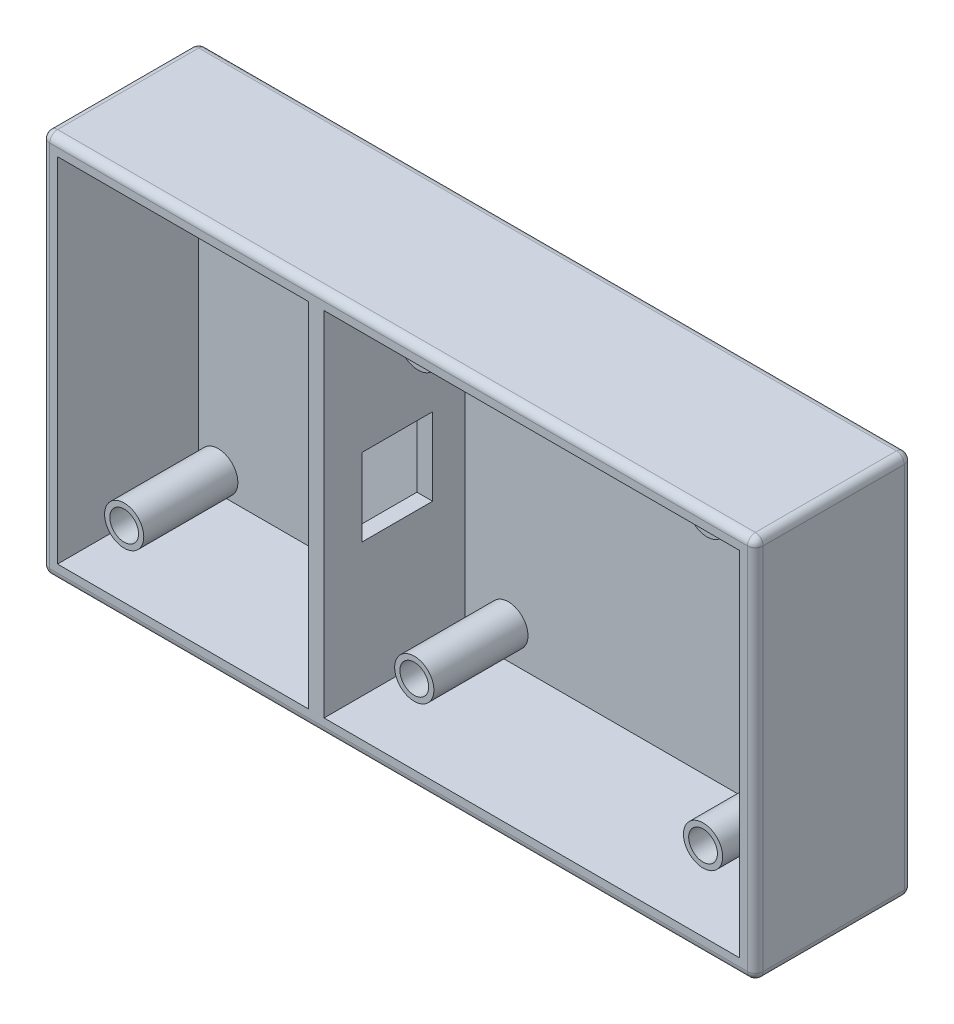
SolidWorks part; units mm, degrees
ref_plane "Front Plane" through (0, 0, 0) normal (0, 0, 1) x (1, 0, 0)
ref_plane "Top Plane" through (0, 0, 0) normal (0, 1, 0) x (1, 0, 0)
ref_plane "Right Plane" through (0, 0, 0) normal (1, 0, 0) x (0, 0, -1)
sketch "Sketch1" plane through (0, 0, 0) normal (0, 0, 1) x (1, 0, 0)
  line L1 (0, 0) -> (91, 0)
  line L2 (0, 0) -> (0, 49)
  line L3 (0, 49) -> (91, 49)
  line L4 (91, 0) -> (91, 49)
  dimension "D1" = 91
  dimension "D2" = 49
extrude "Boss-Extrude1" add sketch "Sketch1" along normal blind 20
shell "Shell1" thickness 2 removed face at (45.5, 24.5, 20)
sketch "Sketch4" plane through (0, 0, 2) normal (0, 0, 1) x (1, 0, 0)
  line L0 (89, 47) -> (2, 47) construction
  line L1 (34, 47) -> (36, 47)
  line L2 (34, 47) -> (34, 2)
  line L3 (34, 2) -> (36, 2)
  line L4 (36, 47) -> (36, 2)
  line L5 (2, 2) -> (89, 2) construction
  dimension "D1" = 2
  dimension "D2" = 32
extrude "Boss-Extrude2" add sketch "Sketch4" along normal blind 18 contours L2 L1 L4 L3
fillet "Fillet2" radius 1 7 edges at (45.5, 49, 20) (0, 49, 10) (45.5, 49, 0) (91, 0, 10) (91, 24.5, 20) (91, 49, 10) (91, 24.5, 0)
fillet "Fillet3" radius 1 9 edges at (90.7071, 0.2929, 19.7071) (90.7071, 0.2929, 0.2929) (0.2929, 48.7071, 0.2929) (0.2929, 48.7071, 19.7071) (45, 0, 20) (45, 0, 0) (0, 0, 10) (0, 24, 0) (0, 24, 20)
sketch "Sketch21" plane through (34, 0, 0) normal (-1, 0, 0) x (0, 0, 1)
  line L1 (15.1437, 28.9119) -> (6.1634, 28.9119)
  line L2 (15.1437, 28.9119) -> (15.1437, 19.0216)
  line L3 (15.1437, 19.0216) -> (6.1634, 19.0216)
  line L4 (6.1634, 28.9119) -> (6.1634, 19.0216)
extrude "Cut-Extrude1" cut sketch "Sketch21" against normal blind 18
sketch "Sketch22" plane through (0, 0, 0) normal (0, 0, 1) x (1, 0, 0)
  line L0 (89, 2) -> (89, 47) construction
  line L5 (36, 2) -> (89, 2) construction
  line L6 (89, 47) -> (36, 47) construction
  line L11 (36, 47) -> (36, 2) construction
  line L13 (89, 47) -> (36, 47) construction
  line L14 (2, 2) -> (34, 2) construction
  line L15 (2, 47) -> (2, 2) construction
  line L16 (2, 47) -> (2, 2) construction
  line L17 (34, 47) -> (2, 47) construction
  circle A0 centre (86.5, 44.5) radius 2.5
  circle A1 centre (4.5, 44.5) radius 2.5
  circle A2 centre (4.5, 4.5) radius 2.5
  circle A3 centre (86.5, 4.5) radius 2.5
  circle A4 centre (42, 42.915) radius 2.5
  circle A5 centre (78.83, 42.915) radius 2.5
  circle A6 centre (41.5002, 6.085) radius 2.5
  circle A7 centre (78.3302, 6.085) radius 2.5
  point P36 (0, 0)
  dimension "D3" = 2.5
  dimension "D4" = 2.5
  dimension "D5" = 2.5
  dimension "D6" = 2.5
  dimension "D7" = 2.5
  dimension "D8" = 2.5
  dimension "D9" = 2.5
  dimension "D10" = 2.5
  dimension "D2" = 36.83
  dimension "D11" = 36.83
  dimension "D12" = 36.83
  dimension "D13" = 36.83
  dimension "D14" = 4.085
  dimension "D15" = 4.085
  dimension "D16" = 6
extrude "Boss-Extrude10" add sketch "Sketch22" along normal blind 14 separate body contours A6 | A4 | A5 | A2 | A1 | A0 | A7 | A3
shell "Shell4" thickness 0.6667 removed face at (7, 4.5, 14)
shell "Shell5" thickness 0.6667 removed face at (7, 44.5, 14)
shell "Shell6" thickness 0.6667 removed face at (44.5, 42.915, 14)
shell "Shell7" thickness 0.6667 removed face at (44.0002, 6.085, 14)
shell "Shell8" thickness 0.6667 removed face at (81.33, 42.915, 14)
shell "Shell9" thickness 0.6667 removed face at (80.8302, 6.085, 14)
shell "Shell10" thickness 0.6667 removed face at (89, 44.5, 14)
shell "Shell11" thickness 0.6667 removed face at (89, 4.5, 14)
